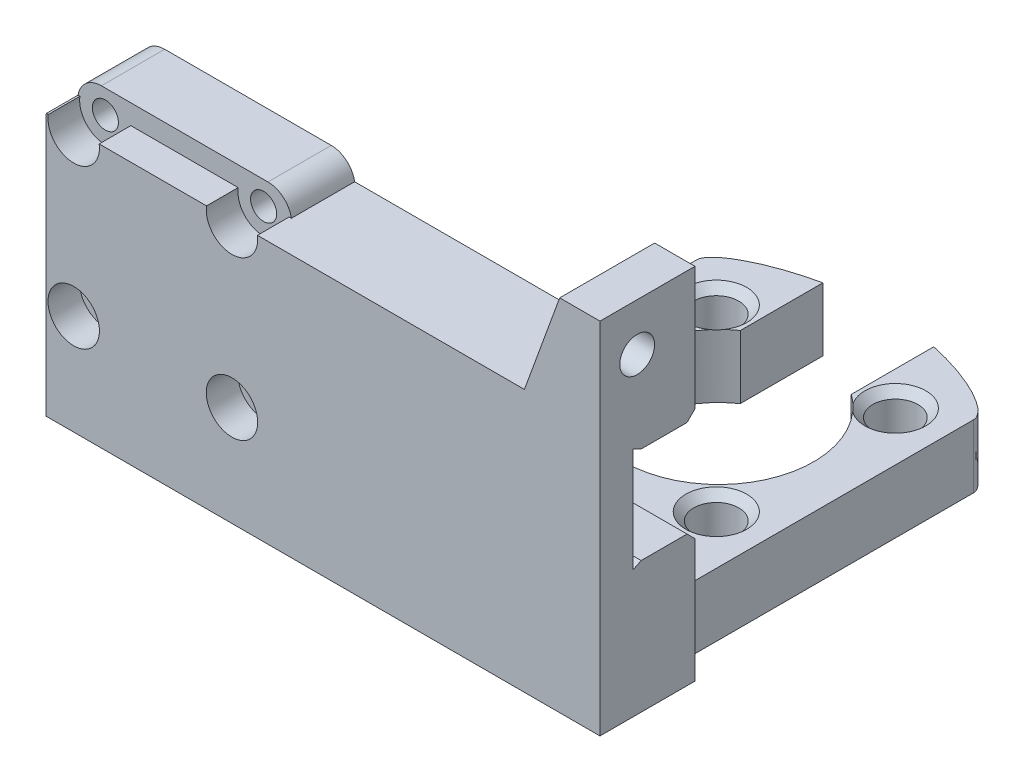
SolidWorks part; units mm, degrees
ref_plane "Front Plane" through (0, 0, 0) normal (0, 0, 1) x (1, 0, 0)
ref_plane "Top Plane" through (0, 0, 0) normal (0, 1, 0) x (1, 0, 0)
ref_plane "Right Plane" through (0, 0, 0) normal (1, 0, 0) x (0, 0, -1)
sketch "Sketch1" plane through (0, 0, 0) normal (0, 0, 1) x (1, 0, 0)
  line L0 (13.5, 32.7) -> (13.5, 12.7) construction
  line L1 (0, 0) -> (70, 0)
  line L2 (0, 0) -> (0, 45.4)
  line L3 (0, 45.4) -> (70, 45.4)
  line L4 (70, 0) -> (70, 45.4)
  line L5 (3.5, 32.7) -> (23.5, 32.7) construction
  line L6 (3.5, 32.7) -> (3.5, 12.7) construction
  line L7 (3.5, 12.7) -> (23.5, 12.7) construction
  line L8 (23.5, 32.7) -> (23.5, 12.7) construction
  circle A0 centre (3.5, 32.7) radius 1.65
  circle A1 centre (23.5, 32.7) radius 1.65
  circle A2 centre (23.5, 12.7) radius 1.65
  circle A3 centre (3.5, 12.7) radius 1.65
  dimension "D3" = 3.3
  dimension "D1" = 45.4
  dimension "D2" = 70
  dimension "D4" = 12.7
  dimension "D5" = 20
  dimension "D6" = 13.5
extrude "Boss-Extrude1" add sketch "Sketch1" along normal blind 12
sketch "Sketch3" plane through (0, 0, 0) normal (0, 0, 1) x (1, 0, 0)
  line L0 (70, 0) -> (70, 45.4) construction
  line L1 (70, 28.8) -> (0, 28.8)
  line L2 (70, 28.8) -> (70, 16.6)
  line L3 (70, 16.6) -> (0, 16.6)
  line L4 (0, 28.8) -> (0, 16.6)
  line L6 (70, 22.7) -> (0, 22.7) construction
  line L7 (0, 45.4) -> (0, 0) construction
  point P6 (0, 22.7)
  point P10 (70, 22.7)
  point P11 (0, 0)
  point P12 (0, 0)
  dimension "D1" = 12.2
extrude "Cut-Extrude1" cut sketch "Sketch3" against normal through all and the other way blind 7.8
sketch "Sketch4" plane through (0, 0, 0) normal (0, 0, -1) x (-1, 0, 0)
  line L0 (-70, 0) -> (-70, 16.6) construction
  line L1 (-67, 0) -> (-32, 0)
  line L2 (-67, 0) -> (-67, 8)
  line L3 (-67, 8) -> (-32, 8)
  line L4 (-32, 0) -> (-32, 8)
  line L7 (0, 0) -> (-70, 0) construction
  dimension "D1" = 8
  dimension "D2" = 35
  dimension "D3" = 3
extrude "Boss-Extrude3" add sketch "Sketch4" along normal blind 44.2
sketch "Sketch5" plane through (0, 8, 0) normal (0, 1, 0) x (1, 0, 0)
  line L1 (70, 0) -> (0, 0) construction
  line L2 (49.5, 44.2) -> (49.5, 0) construction
  line L3 (32, 44.2) -> (67, 44.2) construction
  line L4 (32, 0) -> (67, 0) construction
  circle A0 centre (49.5, 23.5) radius 12
  point P10 (0, 0)
  dimension "D1" = 24
  dimension "D3" = 23.5
extrude "Cut-Extrude2" cut sketch "Sketch5" against normal blind 45
sketch "Sketch6" plane through (0, 16.6, 0) normal (0, -1, 0) x (1, 0, 0)
  circle A3 centre (49.4956, -39.2013) radius 2.85
  circle A4 centre (60.8093, -34.515) radius 2.85
  circle A5 centre (38.1819, -34.515) radius 2.85
  circle A6 centre (38.1819, -11.8876) radius 2.85
  circle A7 centre (60.8093, -11.8876) radius 2.85
  point P4 (0, 0)
  point P5 (0, 0)
  dimension "D1" = 5.7
extrude "Cut-Extrude3" cut sketch "Sketch6" against normal through all both and the other way through all
fillet "Fillet1" radius 6 2 edges at (32, 4, -44.2) (67, 4, -44.2) second distance 15 conic rho 0.3 first distance on face at (32, 4, -22.1) first distance on face at (67, 4, -22.1)
sketch "Sketch8" plane through (0, 0, 12) normal (0, 0, 1) x (1, 0, 0)
  circle A0 centre (3.5, 32.7) radius 3.25
  circle A1 centre (23.5, 32.7) radius 3.25
  circle A2 centre (3.5, 12.7) radius 3.25
  circle A3 centre (23.5, 12.7) radius 3.25
  dimension "D1" = 6.5
extrude "Cut-Extrude5" cut sketch "Sketch8" against normal offset from surface (4 mm away) 8 up to face at (5.15, 12.7, 0)
sketch "Sketch12" plane through (0, 0, 12) normal (0, 0, 1) x (1, 0, 0)
  line L0 (70, 45.4) -> (0, 45.4) construction
  line L5 (0, 45.4) -> (45, 45.4)
  line L6 (0, 45.4) -> (0, 33.15)
  line L7 (0, 33.15) -> (45, 33.15)
  line L8 (45, 45.4) -> (45, 33.15)
  line L9 (0, 45.4) -> (0, 0) construction
  dimension "D1" = 12.25
  dimension "D2" = 45
extrude "Cut-Extrude8" cut sketch "Sketch12" against normal offset from surface (4 mm away) 8 up to face at (5.15, 32.7, 0)
sketch "Sketch13" plane through (0, 8, 0) normal (0, 1, 0) x (1, 0, 0)
  line L1 (56.4956, 50.8384) -> (42.4956, 50.8384)
  line L2 (56.4956, 50.8384) -> (56.4956, 27.5643)
  line L3 (56.4956, 27.5643) -> (42.4956, 27.5643)
  line L4 (42.4956, 50.8384) -> (42.4956, 27.5643)
  line L5 (56.4956, 50.8384) -> (42.4956, 27.5643) construction
  line L6 (56.4956, 27.5643) -> (42.4956, 50.8384) construction
  point P0 (49.4956, 39.2013)
  dimension "D1" = 14
extrude "Cut-Extrude10" cut sketch "Sketch13" against normal blind 10
sketch "Sketch14" plane through (0, 0, 0) normal (0, 0, -1) x (-1, 0, 0)
  line L1 (-70, 28.8) -> (0, 28.8)
  line L2 (-70, 28.8) -> (-70, 16.6)
  line L3 (-70, 16.6) -> (0, 16.6)
  line L4 (0, 28.8) -> (0, 16.6)
extrude "Boss-Extrude5" [suppressed] add sketch "Sketch14" against normal blind 0.5
sketch "Sketch15" plane through (0, 8, 0) normal (0, 1, 0) x (1, 0, 0)
  circle A0 centre (49.4956, 7.2013) radius 2.4
  point P2 (0, 0)
  point P3 (49.4956, 7.1004)
  point P4 (48.896, 6.45)
  point P5 (49.4956, 7.2013)
  point P10 (49.4956, 7.171)
  point P11 (49.4956, 7.086)
  dimension "D1" = 4.8
extrude "Boss-Extrude6" add sketch "Sketch15" along normal blind 2
sketch "Sketch16" plane through (0, 45.4, 0) normal (0, 1, 0) x (1, 0, 0)
  line L0 (32, 0) -> (67, 0) construction
  line L1 (65, 0) -> (27, 0)
  line L2 (65, 0) -> (65, -12)
  line L3 (65, -12) -> (27, -12)
  line L4 (27, 0) -> (27, -12)
  line L5 (70, -12) -> (45, -12) construction
  line L6 (70, -12) -> (70, 0) construction
  line L8 (0, -8) -> (0, 0) construction
  point P10 (0, 0)
  point P13 (0, -4)
  dimension "D1" = 27
  dimension "D2" = 5
extrude "Cut-Extrude11" cut sketch "Sketch16" against normal up to surface (12.25 mm away) up to face at (35.8593, 33.15, 10)
chamfer "Chamfer2" distance 12.5 angle 20 1 edges at (65, 33.15, 6) first distance on face at (65, 39.275, 6)
sketch "Sketch17" plane through (70, 0, 0) normal (1, 0, 0) x (0, 0, -1)
  line L0 (-12, 45.4) -> (0, 45.4) construction
  line L1 (-12, 0) -> (-12, 45.4) construction
  circle A0 centre (-7.3, 39.4) radius 2.2
  dimension "D1" = 4.4
  dimension "D2" = 6
  dimension "D3" = 4.7
extrude "Cut-Extrude12" cut sketch "Sketch17" against normal blind 10
sketch "Sketch18" plane through (70, 0, 0) normal (1, 0, 0) x (0, 0, -1)
  line L0 (-7.8, 28.8) -> (-6.8, 28.8)
  line L1 (-7.8, 28.8) -> (0, 28.8) construction
  line L2 (-6.8, 28.8) -> (-7.8, 29.3)
  line L3 (-7.8, 29.3) -> (-7.8, 28.8)
  line L4 (-7.8, 16.6) -> (-7.8, 16.1)
  line L5 (-7.8, 16.1) -> (-6.8, 16.6)
  line L6 (-7.8, 16.6) -> (0, 16.6) construction
  line L7 (-6.8, 16.6) -> (-7.8, 16.6)
  dimension "D1" = 0.5
  dimension "D2" = 1
  dimension "D3" = 1
  dimension "D4" = 0.5
extrude "Cut-Extrude13" cut sketch "Sketch18" against normal through all
sketch "Sketch19" plane through (0, 0, 0) normal (0, 0, -1) x (-1, 0, 0)
  line L0 (-70, 0) -> (-70, 16.6) construction
  line L1 (-75, 34.8) -> (-70, 34.8)
  line L2 (-75, 34.8) -> (-75, 10.6)
  line L3 (-75, 10.6) -> (-70, 10.6)
  line L4 (-70, 34.8) -> (-70, 10.6)
  line L5 (0, 16.6) -> (-70, 16.6) construction
  line L6 (-70, 28.8) -> (0, 28.8) construction
  dimension "D1" = 6
  dimension "D2" = 6
extrude "Boss-Extrude7" [suppressed] add sketch "Sketch19" along normal blind 5
sketch "Sketch20" [suppressed] plane through (80, 0, 0) normal (1, 0, 0) x (0, 0, -1)
  line L0 (0, 28.8) -> (0, 16.6)
  line L1 (0, 28.8) -> (1, 28.8)
  line L2 (0, 16.6) -> (1, 16.6)
  line L3 (1, 28.8) -> (1, 16.6)
  dimension "D1" = 1
extrude "Cut-Extrude14" [suppressed] cut sketch "Sketch20" against normal through all
fillet "Fillet3" [suppressed] radius 13
chamfer "Chamfer1" distance 1.9 angle 45 1 edges at (49.4956, 10, -4.8013)
sketch "Sketch21" plane through (0, 0, 8) normal (0, 0, 1) x (1, 0, 0)
  line L0 (27, 33.15) -> (27, 45.4) construction
  line L1 (0, 45.4) -> (27, 45.4)
  line L2 (0, 45.4) -> (0, 35.65)
  line L3 (0, 35.65) -> (27, 35.65)
  line L4 (27, 45.4) -> (27, 35.65)
  line L5 (6.7187, 33.15) -> (20.2813, 33.15) construction
  dimension "D1" = 2.5
extrude "Cut-Extrude15" cut sketch "Sketch21" against normal through all
fillet "Fillet4" radius 3 2 edges at (0, 35.65, 4) (27, 35.65, 4)
chamfer "Chamfer3" distance 3 angle 45 2 edges at (67, 4, 0) (32, 4, 0)
chamfer "Chamfer4" distance 1 angle 45 4 edges at (60.8093, 8, -14.7376) (38.1819, 8, -14.7376) (60.8093, 8, -37.365) (38.1819, 8, -37.365)
chamfer "Chamfer5" distance 1 angle 45 2 edges at (35, 16.6, 0) (35, 28.8, 0)
